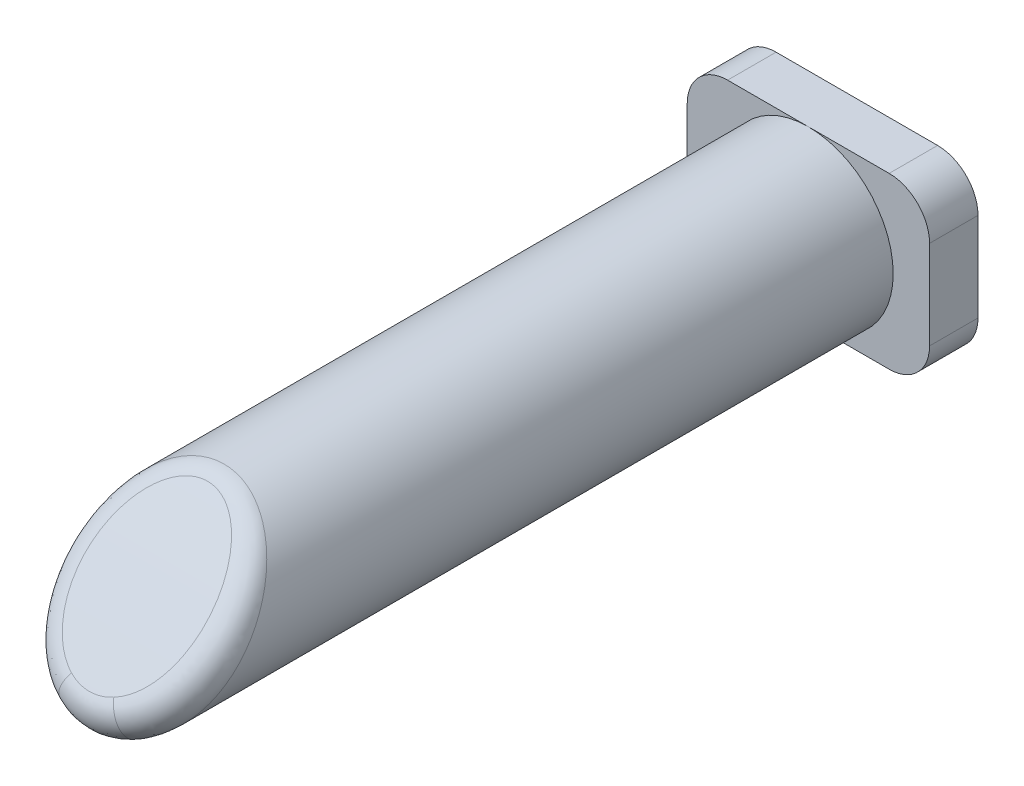
SolidWorks part; units mm, degrees
ref_plane "Plan de face" through (0, 0, 0) normal (0, 0, 1) x (1, 0, 0)
ref_plane "Plan de dessus" through (0, 0, 0) normal (0, 1, 0) x (1, 0, 0)
ref_plane "Plan de droite" through (0, 0, 0) normal (1, 0, 0) x (0, 0, -1)
sketch "Esquisse1" plane through (0, 0, 0) normal (0, 0, 1) x (1, 0, 0)
  line L1 (-6, 4.2) -> (0, 4.2)
  line L2 (-6, 4.2) -> (-6, 0)
  line L3 (-6, 0) -> (0, 0)
  line L4 (0, 4.2) -> (0, 0)
  dimension "D1" = 4.2
  dimension "D2" = 6
extrude "Boss.-Extru.1" add sketch "Esquisse1" along normal blind 1.2
sketch "Esquisse2" plane through (0, 0, 1.2) normal (0, 0, 1) x (1, 0, 0)
  line L0 (0, 0) -> (0, 4.2) construction
  line L1 (0, 4.2) -> (-6, 4.2) construction
  circle A0 centre (-3, 2.1) radius 2.1
  dimension "D1" = 3
  dimension "D3" = 4.2
  dimension "D2" = 2.1
extrude "Boss.-Extru.2" add sketch "Esquisse2" along normal blind 18.5
sketch "Esquisse4" plane through (0, 0, 0) normal (1, 0, 0) x (0, 0, -1)
  line L1 (-1.2, 4.2) -> (-1.2, 0) construction
  line L2 (3.9731, 14.47) -> (2.3617, 22.1931)
  line L3 (-29.2446, -25.7304) -> (-28.814, 1.1177)
  arc A0 (3.9731, 14.47) -> (-29.2446, -25.7304) centre (12.5, -26.4) ccw
  arc A1 (2.3617, 22.1931) -> (-28.814, 1.1177) centre (12.5, -26.4) ccw
  point P4 (-1.2, 2.1)
  dimension "D1" = 83.5
  dimension "D2" = 28.5
extrude "Enlèv. mat.-Extru.1" cut sketch "Esquisse4" against normal blind 10
fillet "Congé1" radius 0.6 2 edges at (-3, 0.1748, 19.7) (-3.052, 4.1994, 15.9032)
fillet "Congé2" radius 1 4 edges at (-6, 4.2, 0.6) (0, 4.2, 0.6) (-6, 0, 0.6) (0, 0, 0.6)
